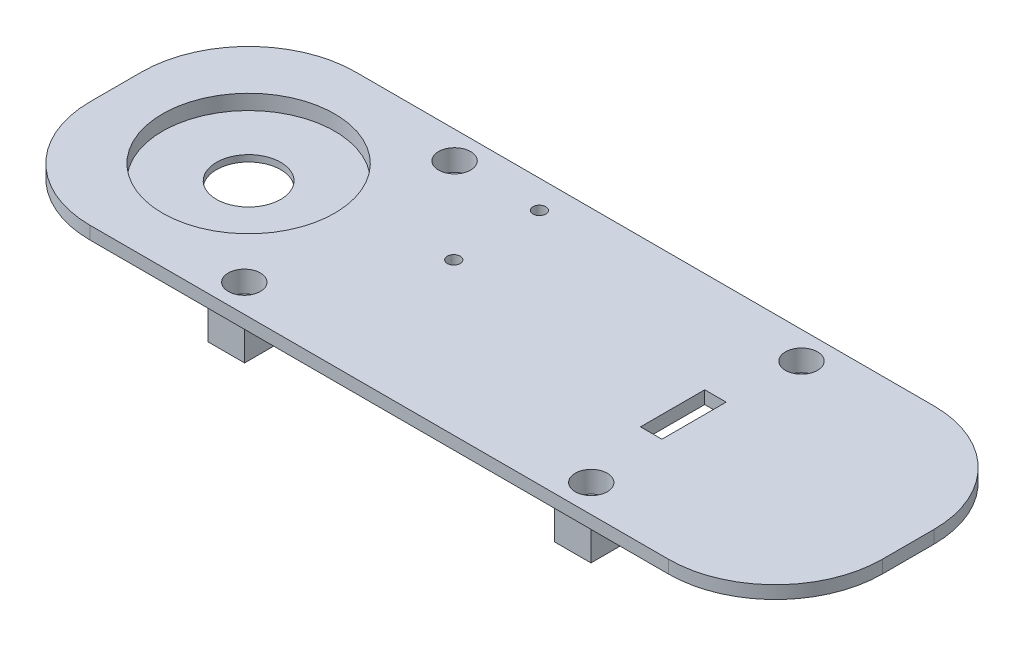
SolidWorks part; units mm, degrees
note: The reader was unsure of these and kept them because the rebuilt part matched: shared geometry of "Sketch28<2>", "Sketch35<5>", "Sketch35<6>", "Sketch36<5>".
ref_plane "Front Plane" through (0, 0, 0) normal (0, 0, 1) x (1, 0, 0)
ref_plane "Top Plane" through (0, 0, 0) normal (0, 1, 0) x (1, 0, 0)
ref_plane "Right Plane" through (0, 0, 0) normal (1, 0, 0) x (0, 0, -1)
sketch "Sketch1" plane through (0, 0, 0) normal (0, 1, 0) x (1, 0, 0)
  line L1 (0, 0) -> (185, 0)
  line L2 (0, 0) -> (0, 62)
  line L3 (0, 62) -> (185, 62)
  line L4 (185, 0) -> (185, 62)
  dimension "D1" = 185
  dimension "D2" = 62
extrude "Boss-Extrude1" add sketch "Sketch1" along normal blind 70
fillet "Fillet1" radius 25 4 edges at (185, 35, -62) (185, 35, 0) (0, 35, -62) (0, 35, 0)
ref_plane "Plane1" through (0, 67, 0) normal (0, 1, 0) x (1, 0, 0)
sketch "Sketch7" plane through (0, 67, 0) normal (0, 1, 0) x (1, 0, 0)
  line L0 (25, 58) -> (160, 58)
  line L1 (25, 4) -> (160, 4)
  line L2 (181, 37) -> (181, 25)
  line L3 (4, 37) -> (4, 25)
  line L5 (185, 25) -> (185, 37) construction
  arc A1 (25, 58) -> (4, 37) centre (25, 37) ccw
  arc A2 (25, 4) -> (4, 25) centre (25, 25) cw
  arc A3 (160, 4) -> (181, 25) centre (160, 25) ccw
  arc A4 (160, 58) -> (181, 37) centre (160, 37) cw
  dimension "D1" = 4
extrude "Cut-Extrude6" cut sketch "Sketch7" against normal blind 64
sketch "Sketch11" plane through (0, 0, 0) normal (0, -1, 0) x (1, 0, 0)
  line L0 (185, -25) -> (185, -37) construction
  line L1 (160, -62) -> (25, -62) construction
  circle A0 centre (154, -31) radius 25
  dimension "D1" = 50
  dimension "D2" = 31
  dimension "D3" = 31
extrude "Cut-Extrude9" cut sketch "Sketch11" against normal blind 17
sketch "Sketch16" plane through (0, 70, 0) normal (0, 1, 0) x (1, 0, 0)
  line L0 (25, 0) -> (160, 0) construction
  line L1 (0, 37) -> (0, 25) construction
  circle A0 centre (31, 31) radius 21
  dimension "D1" = 42
  dimension "D2" = 31
  dimension "D3" = 31
extrude "Boss-Extrude6" add sketch "Sketch16" against normal blind 5
sketch "Sketch17" plane through (0, 70, 0) normal (0, 1, 0) x (1, 0, 0)
  line L0 (0, 37) -> (0, 25) construction
  line L1 (25, 0) -> (160, 0) construction
  circle A0 centre (31, 31) radius 20.1
  dimension "D3" = 40.2
  dimension "D1" = 31
  dimension "D2" = 31
extrude "Cut-Extrude12" cut sketch "Sketch17" against normal blind 3.5
sketch "Sketch20" plane through (0, 0, 0) normal (0, -1, 0) x (1, 0, 0)
  line L0 (0, -37) -> (0, -25) construction
  line L1 (160, -62) -> (25, -62) construction
  circle A0 centre (31, -31) radius 25
  dimension "D3" = 50
  dimension "D1" = 31
  dimension "D2" = 31
extrude "Cut-Extrude14" cut sketch "Sketch20" against normal blind 5.5
sketch "Sketch25" plane through (0, 0, 0) normal (-1, 0, 0) x (0, 0, 1)
  line L0 (-37, 70) -> (-25, 70) construction
  line L1 (-51, 39) -> (-11, 39)
  line L2 (-51, 39) -> (-51, 31)
  line L3 (-51, 31) -> (-11, 31)
  line L4 (-11, 39) -> (-11, 31)
  line L5 (-25, 0) -> (-25, 70) construction
  point P4 (-31, 39)
  point P7 (-31, 70)
  point P8 (-11, 35)
  point P11 (-25, 35)
  dimension "D1" = 8
  dimension "D2" = 40
extrude "Cut-Extrude16" cut sketch "Sketch25" against normal blind 14
sketch "Sketch27" plane through (0, 67, 0) normal (0, 1, 0) x (1, 0, 0)
  line L0 (4.02, 37) -> (4.02, 25)
  line L3 (31, 31) -> (197.2271, 31) construction
  line L4 (31, 73.5576) -> (197.2271, 73.5576)
  line L5 (31, -11.5576) -> (197.2271, -11.5576)
  line L6 (25, 57.98) -> (160, 57.98)
  line L7 (25, 4.02) -> (160, 4.02)
  line L8 (180.98, 37) -> (180.98, 25)
  line L9 (25, 0) -> (160, 0) construction
  arc A2 (31, 73.5576) -> (31, -11.5576) centre (31, 31) ccw
  arc A3 (197.2271, -11.5576) -> (197.2271, 73.5576) centre (197.2271, 31) ccw
  arc A4 (25, 57.98) -> (4.02, 37) centre (25, 37) ccw
  arc A5 (25, 4.02) -> (4.02, 25) centre (25, 25) cw
  arc A6 (180.98, 25) -> (160, 4.02) centre (160, 25) cw
  arc A7 (160, 57.98) -> (180.98, 37) centre (160, 37) cw
  point P10 (114.1135, 31)
  dimension "D1" = 4.02
extrude "Cut-Extrude21" cut sketch "Sketch27" against normal blind 0.1
sketch "Sketch28" plane through (0, 0, 0) normal (0, -1, 0) x (1, 0, 0)
  line L0 (25, 0) -> (160, 0)
  line L1 (185, -25) -> (185, -37)
  line L2 (160, -62) -> (25, -62)
  line L3 (0, -37) -> (0, -25)
  arc A0 (0, -25) -> (25, 0) centre (25, -25) cw
  arc A1 (0, -37) -> (25, -62) centre (25, -37) ccw
  arc A2 (185, -37) -> (160, -62) centre (160, -37) cw
  arc A3 (160, 0) -> (185, -25) centre (160, -25) cw
  circle A4 centre (31, -31) radius 25
  circle A5 centre (154, -31) radius 25
  circle A6 centre (31, -31) radius 25 construction
  circle A7 centre (154, -31) radius 25 construction
extrude "Boss-Extrude10" add sketch "Sketch28" along normal blind 1
sketch "Sketch29" plane through (0, 70, 0) normal (0, 1, 0) x (1, 0, 0)
  line L0 (185, 25) -> (185, 37) construction
  line L1 (130, 38.5) -> (135, 38.5)
  line L2 (130, 38.5) -> (130, 23.5)
  line L3 (130, 23.5) -> (135, 23.5)
  line L4 (135, 38.5) -> (135, 23.5)
  point P6 (135, 31)
  point P7 (185, 31)
  dimension "D1" = 15
  dimension "D2" = 5
  dimension "D3" = 50
extrude "Cut-Extrude22" cut sketch "Sketch29" against normal blind 5
extrude "Cut-Extrude24" cut sketch "Sketch28<2>" against normal blind 44 and the other way blind 73
sketch "Sketch28<2>" plane through (0, 0, 0) normal (0, -1, 0) x (1, 0, 0) same geometry as "Sketch28"
sketch "Sketch33" plane through (0, 44, 0) normal (0, -1, 0) x (1, 0, 0)
  line L0 (25, -4) -> (160, -4)
  line L1 (160, -4) -> (25, -4) construction
  line L2 (181, -25) -> (181, -37)
  line L3 (160, -58) -> (25, -58)
  line L4 (4, -37) -> (4, -25)
  arc A0 (181, -25) -> (160, -4) centre (160, -25) ccw construction
  arc A1 (160, -4) -> (181, -25) centre (160, -25) cw
  arc A2 (181, -37) -> (160, -58) centre (160, -37) cw
  arc A3 (25, -58) -> (4, -37) centre (25, -37) cw
  arc A4 (4, -25) -> (25, -4) centre (25, -25) cw
extrude "Cut-Extrude25" cut sketch "Sketch33" against normal up to surface (23 mm away) flip side to cut up to face at (132.5, 67, -31)
sketch "Sketch35" plane through (0, 70, 0) normal (0, 1, 0) x (1, 0, 0)
  line L0 (58.8633, 10.7) -> (50.3633, 2.2) construction
  line L1 (50.3633, 59.8) -> (58.8633, 59.8)
  line L2 (50.3633, 59.8) -> (50.3633, 51.3)
  line L3 (50.3633, 51.3) -> (58.8633, 51.3)
  line L4 (58.8633, 59.8) -> (58.8633, 51.3)
  line L5 (131.2381, 59.8) -> (139.7381, 59.8)
  line L6 (131.2381, 59.8) -> (131.2381, 51.3)
  line L7 (131.2381, 51.3) -> (139.7381, 51.3)
  line L8 (139.7381, 59.8) -> (139.7381, 51.3)
  line L9 (50.3633, 10.7) -> (58.8633, 10.7)
  line L10 (50.3633, 10.7) -> (50.3633, 2.2)
  line L11 (50.3633, 2.2) -> (58.8633, 2.2)
  line L12 (58.8633, 10.7) -> (58.8633, 2.2)
  line L13 (131.2381, 10.7) -> (139.7381, 10.7)
  line L14 (131.2381, 10.7) -> (131.2381, 2.2)
  line L15 (131.2381, 2.2) -> (139.7381, 2.2)
  line L16 (139.7381, 10.7) -> (139.7381, 2.2)
  line L17 (25, 0) -> (160, 0) construction
  line L18 (160, 62) -> (25, 62) construction
  line L21 (131.2381, 2.2) -> (139.7381, 10.7) construction
  line L22 (131.2381, 51.3) -> (139.7381, 59.8) construction
  line L23 (50.3633, 51.3) -> (58.8633, 59.8) construction
  circle A6 centre (54.5, 6.5) radius 3.75
  circle A8 centre (135.5, 6.5) radius 3.75
  circle A9 centre (135.5, 55.5921) radius 3.75
  circle A10 centre (54.5, 55.5921) radius 3.75
  circle A11 centre (54.5, 6.5) radius 2.1
  circle A12 centre (135.5, 6.5) radius 2.1
  circle A13 centre (135.5, 55.5921) radius 2.1
  circle A14 centre (54.5, 55.5921) radius 2.1
  circle A15 centre (31, 31) radius 20.1 construction
  dimension "D1" = 7.5
  dimension "D7" = 4.2
  dimension "D2" = 23.5
  dimension "D3" = 2.2
  dimension "D4" = 2.2
  dimension "D5" = 8.5
extrude "Boss-Extrude16" add sketch "Sketch35" against normal blind 12 contours L4 L1 L2 L3 A10 | A10 A14 | A6 A11 | L12 L9 L10 L11 A6 | A8 A12 | L16 L13 L14 L15 A8 | A9 A13 | L8 L5 L6 L7 A9
sketch "Sketch18" plane through (0, 70, 0) normal (0, 1, 0) x (1, 0, 0)
  circle A0 centre (31, 31) radius 7.5
  dimension "D1" = 15
extrude "Cut-Extrude13" cut sketch "Sketch18" against normal through all both and the other way through all
extrude "Cut-Extrude36" cut sketch "Sketch35<5>" against normal blind 5 contours A6 A11 | A10 A14 | A9 A13 | A8 A12
sketch "Sketch35<5>" plane through (0, 70, 0) normal (0, 1, 0) x (1, 0, 0) same geometry as "Sketch35"
extrude "Cut-Extrude37" cut sketch "Sketch35<6>" against normal through all both and the other way through all contours A11 | A14 | A13 | A12
sketch "Sketch35<6>" plane through (0, 70, 0) normal (0, 1, 0) x (1, 0, 0) same geometry as "Sketch35"
sketch "Sketch36" plane through (0, 70, 0) normal (0, -1, 0) x (1, 0, 0)
  line L0 (74.426, -35.4691) -> (74.426, -55.4691) construction
  line L5 (76.926, -52.9691) -> (76.926, -57.9691)
  line L6 (45.5, -55.5) -> (85.3425, -55.5) construction
  line L12 (76.9271, -38.2364) -> (71.9271, -38.2364)
  line L13 (76.9271, -38.2364) -> (76.9271, -33.2364)
  line L14 (76.9271, -33.2364) -> (71.9271, -33.2364)
  line L15 (71.9271, -38.2364) -> (71.9271, -33.2364)
  line L16 (76.9271, -38.2364) -> (71.9271, -33.2364) construction
  line L17 (76.9271, -33.2364) -> (71.9271, -38.2364) construction
  line L18 (76.926, -57.9691) -> (71.926, -57.9691)
  line L19 (71.926, -57.9691) -> (71.926, -52.9691)
  line L20 (71.926, -52.9691) -> (76.926, -52.9691)
  line L21 (71.926, -52.9691) -> (76.926, -57.9691) construction
  circle A1 centre (74.426, -55.4691) radius 1.5
  circle A2 centre (74.426, -35.4691) radius 1.5
  dimension "D2" = 5
  dimension "D6" = 3
  dimension "D1" = 20
extrude "Boss-Extrude17" add sketch "Sketch36" along normal blind 9
extrude "Cut-Extrude38" cut sketch "Sketch36<5>" along normal blind 9 contours A1 | A2
sketch "Sketch36<5>" plane through (0, 70, 0) normal (0, -1, 0) x (1, 0, 0) same geometry as "Sketch36"
